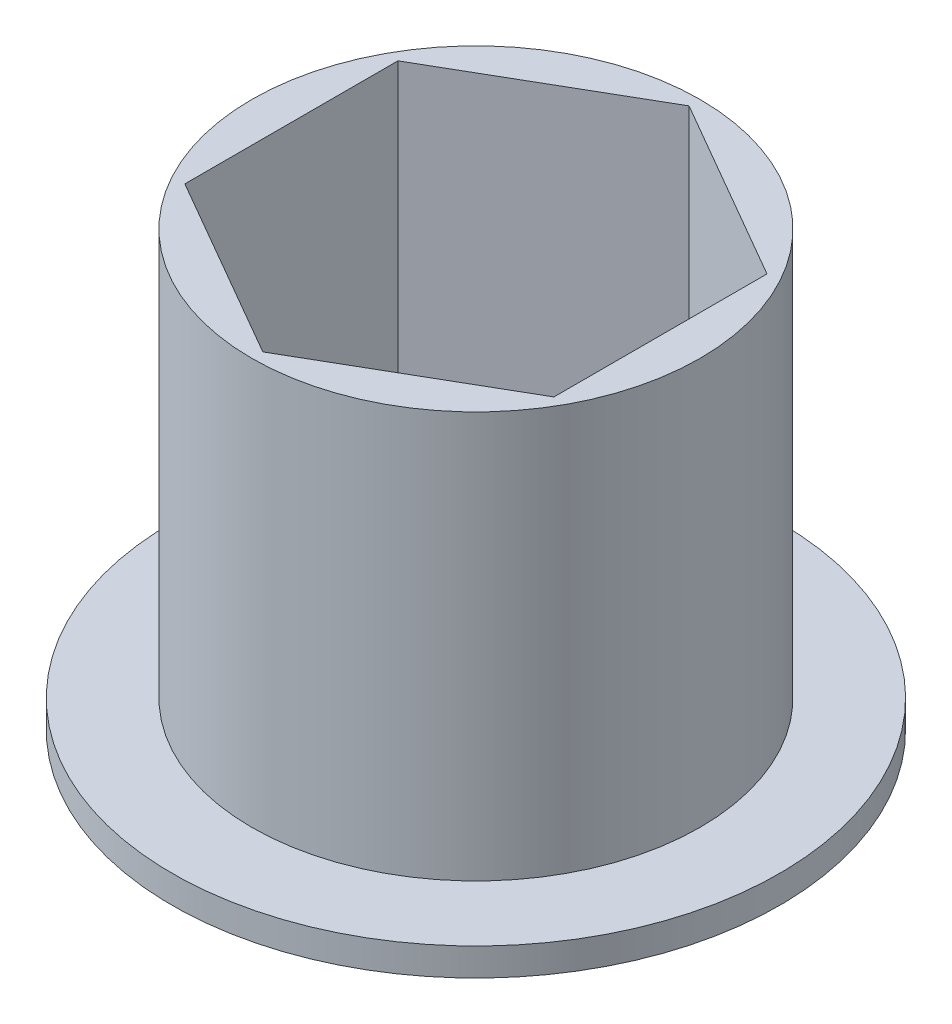
SolidWorks part; units mm, degrees
ref_plane "Front Plane" through (0, 0, 0) normal (0, 0, 1) x (1, 0, 0)
ref_plane "Top Plane" through (0, 0, 0) normal (0, 1, 0) x (1, 0, 0)
ref_plane "Right Plane" through (0, 0, 0) normal (1, 0, 0) x (0, 0, -1)
sketch "Sketch1" plane through (0, 0, 0) normal (0, 1, 0) x (1, 0, 0)
  line L1 (0, 5.8457) -> (-5.0625, 2.9228)
  line L2 (-5.0625, 2.9228) -> (-5.0625, -2.9228)
  line L3 (-5.0625, -2.9228) -> (0, -5.8457)
  line L4 (0, -5.8457) -> (5.0625, -2.9228)
  line L5 (5.0625, -2.9228) -> (5.0625, 2.9228)
  line L6 (5.0625, 2.9228) -> (0, 5.8457)
  circle A0 centre (0, 0) radius 6.15
  circle A1 centre (0, 0) radius 5.0625 construction
  circle A2 centre (0, 0) radius 8.3344
  dimension "D1" = 10.125
  dimension "D2" = 12.3
  dimension "D3" = 16.6687
extrude "Boss-Extrude1" add sketch "Sketch1" along normal blind 11.9062 contours A0 L6 L5 L4 L3 L2 L1 region at (-5.9761, 0, 0)
extrude "Boss-Extrude2" add sketch "Sketch1<3>" along normal blind 0.762 contours A2 A0 region at (-8.0986, 0, 0)
sketch "Sketch1<3>" plane through (0, 0, 0) normal (0, 1, 0) x (1, 0, 0) same geometry as "Sketch1"
